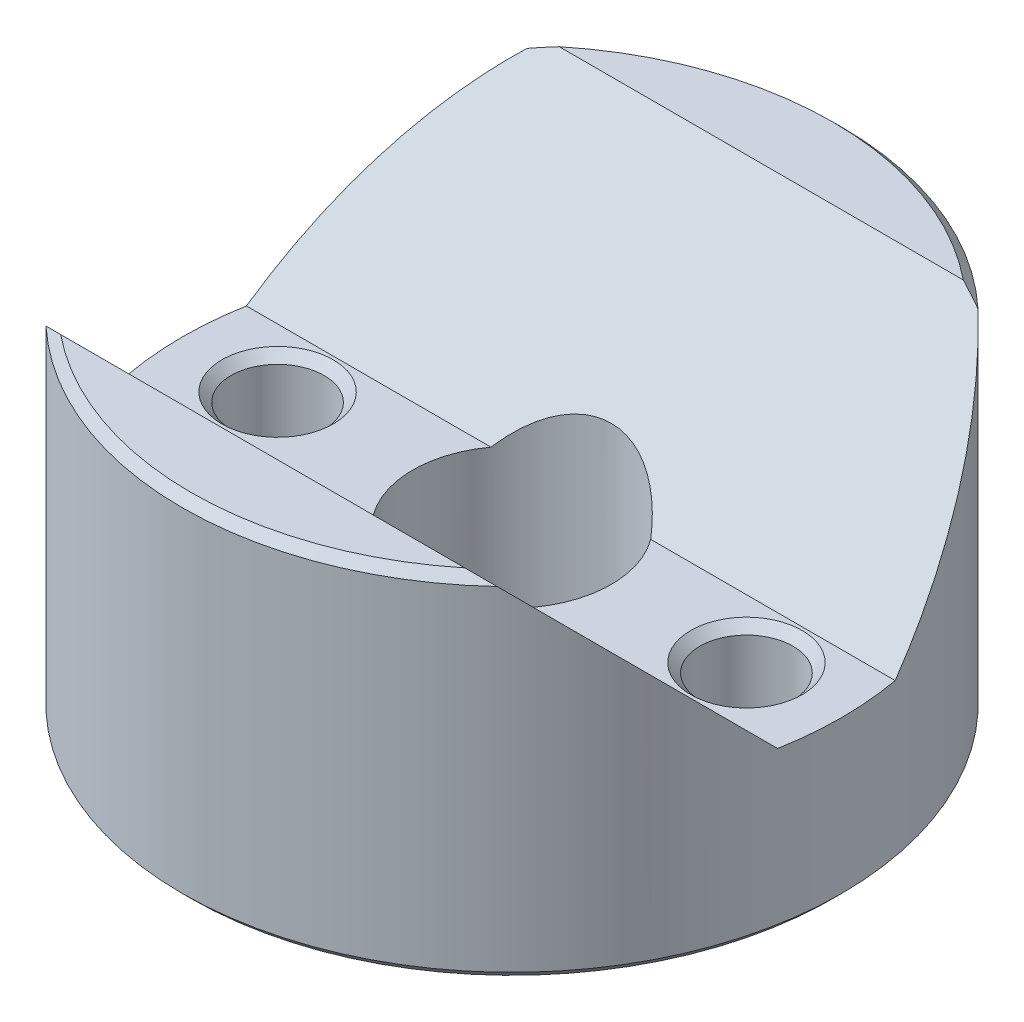
SolidWorks part; units mm, degrees
ref_plane "Plane X-Y" through (0, 0, 0) normal (0, 0, 1) x (1, 0, 0)
ref_plane "Plane X-Z" through (0, 0, 0) normal (0, 1, 0) x (1, 0, 0)
ref_plane "Plane Y-Z" through (0, 0, 0) normal (1, 0, 0) x (0, 0, -1)
ref_axis "Axis - X" through (-15.7163, 0, 0) along (1, 0, 0)
ref_axis "Axis - Y" through (0, 16.002, 0) along (0, -1, 0)
ref_axis "Axis - Z" through (0, 0, -15.7163) along (0, 0, 1)
sketch "Sketch1" plane through (0, 0, 0) normal (0, 1, 0) x (1, 0, 0)
  circle A0 centre (0, 0) radius 14.2875
  dimension "D1" = 28.575
extrude "Extrude1" add sketch "Sketch1" along normal blind 15.24
sketch "Sketch3" plane through (0, 0, 0) normal (1, 0, 0) x (0, 0, -1)
  line L0 (-10.8034, 15.24) -> (10.8034, 15.24)
  line L1 (14.2875, 15.24) -> (-14.2875, 15.24) construction
  line L2 (10.8034, 15.24) -> (2.5484, 6.985)
  line L3 (2.5484, 6.985) -> (-2.5484, 6.985)
  line L4 (-2.5484, 6.985) -> (-10.8034, 15.24)
  line L5 (-14.2875, 0) -> (14.2875, 0) construction
  circle A0 centre (0, 22.3971) radius 12.7 construction
  circle A1 centre (0, 17.907) radius 9.525 construction
  circle A2 centre (0, 15.6619) radius 7.9375 construction
  point P4 (0, 6.985)
  point P8 (0, 15.24)
  dimension "D3" = 25.4
  dimension "D4" = 35.0971
  dimension "D6" = 19.05
  dimension "D7" = 15.875
  dimension "D9" = 23.5994
  dimension "D1" = 21.6068
  dimension "D2" = 6.985
  dimension "D5" = 5.0968
  dimension "D8" = 27.432
extrude "Cut-Extrude1" cut sketch "Sketch3" against normal through all and the other way through all
hole_wizard "Tap Drill for #10 Tap1" positions "Sketch5" profile "Sketch4" hole size "#10-32" standard "Ansi Inch" end condition through all
sketch "Sketch5" plane through (0, 0, 0) normal (0, -1, 0) x (1, 0, 0)
  line L0 (10.16, 0) -> (-10.16, 0) construction
  point P0 (-10.16, 0)
  point P1 (10.16, 0)
  dimension "D1" = 20.32
sketch "Sketch4" plane through (-10.16, 0, 0) normal (1, 0, 0) x (0, 0, -1)
  line L0 (0, 0) -> (0, 15.24)
  line L1 (0, 15.24) -> (2.0193, 15.24)
  line L2 (2.0193, 15.24) -> (2.0193, 0)
  line L5 (2.0193, 0) -> (0, 0)
  line L11 (0, -6.35) -> (0, 107.95) construction
  dimension "Thru Hole Dia." = 4.0386
  dimension "Thru Hole Depth" = 15.24
cosmetic thread "Cosmetic Thread1" parameters "D2"=4.826
cosmetic thread "Cosmetic Thread2" parameters "D2"=4.826
chamfer "Chamfer1" distance 0.3937 angle 45 4 edges at (10.16, 6.985, -2.0193) (10.16, 0, -2.0193) (-10.16, 6.985, -2.0193) (-10.16, 0, -2.0193)
sketch "Sketch6" plane through (0, 0, 0) normal (0, -1, 0) x (1, 0, 0)
  circle A0 centre (0, 0) radius 6.35
  dimension "D1" = 12.7
extrude "Cut-Extrude2" cut sketch "Sketch6" against normal blind 0.635
chamfer "Chamfer2" distance 0.635 angle 45 1 edges at (0, 0.635, -6.35)
sketch "Sketch9" plane through (0, 0, 0) normal (0, 0, 1) x (1, 0, 0)
  line L0 (0, 0) -> (0, 7.5502) construction
  line L1 (12.573, 6.985) -> (14.2875, 6.985)
  line L2 (2.032, 6.985) -> (1.5875, 6.5405)
  line L3 (-7.747, 6.985) -> (7.747, 6.985)
  line L4 (0, 6.985) -> (2.032, 6.985)
  line L5 (-14.2875, 6.985) -> (-12.573, 6.985)
  line L6 (1.5875, 6.5405) -> (1.5875, 0.9525)
  line L7 (1.5875, 0.9525) -> (1.905, 0.635)
  line L8 (-5.715, 0.635) -> (5.715, 0.635)
  line L9 (0, 0.635) -> (1.905, 0.635)
  line L10 (0, 6.985) -> (0, 0.635)
  dimension "D1" = 3.175
  dimension "D2" = 45
  dimension "D3" = 4.064
  dimension "D4" = 3.81
revolve "Cut-Revolve1" cut sketch "Sketch9" angle 360 about L0
chamfer "Chamfer3" distance 0.381 angle 45 3 edges at (0, 0, 14.2875) (0, 15.24, -14.2875) (0, 15.24, 14.2875)
hole_wizard "Ø8.6 (8.6) Diameter Hole1" positions "Sketch11" profile "Sketch10" hole size "Ø8.6" standard "ANSI Metric"
sketch "Sketch11" plane through (0, 0.635, 0) normal (0, -1, 0) x (1, 0, 0)
  point P0 (0, 0)
sketch "Sketch10" plane through (0, 0.635, 0) normal (1, 0, 0) x (0, 0, -1)
  line L0 (0, 0) -> (0, 17.8237)
  line L1 (0, 17.8237) -> (4.3, 15.24)
  line L2 (4.3, 15.24) -> (4.3, 0)
  line L5 (4.3, 0) -> (0, 0)
  line L10 (0, 17.8237) -> (-4.3, 15.24) construction
  line L11 (0, -6.35) -> (0, 107.95) construction
  dimension "Hole Dia." = 8.6
  dimension "Hole Depth" = 15.24
  dimension "Drill Angle" = 118
